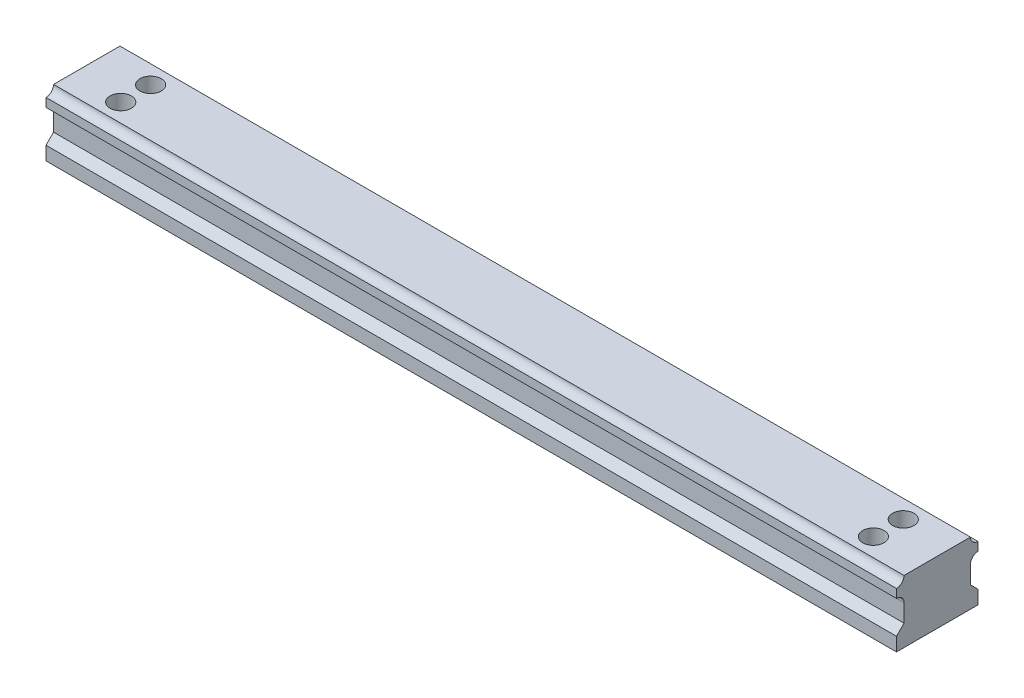
SolidWorks part; units mm, degrees
ref_plane "Front Plane" through (0, 0, 0) normal (0, 0, 1) x (1, 0, 0)
ref_plane "Top Plane" through (0, 0, 0) normal (0, 1, 0) x (1, 0, 0)
ref_plane "Right Plane" through (0, 0, 0) normal (1, 0, 0) x (0, 0, -1)
sketch "Sketch1" plane through (0, 0, 0) normal (1, 0, 0) x (0, 0, -1)
  line L0 (0, 0) -> (30, 0)
  line L1 (0, 0) -> (0, 5)
  line L2 (0, 5) -> (2.7781, 7.7781)
  line L3 (2.7781, 7.7781) -> (2.7781, 14.2781)
  line L4 (2.7781, 14.2781) -> (0, 14.2781) construction
  line L5 (0, 14.2781) -> (0, 23) construction
  line L6 (0, 23) -> (30, 23) construction
  line L12 (15, 0) -> (15, 23) construction
  line L13 (27.2219, 23) -> (2.7781, 23)
  line L14 (0, 20.2219) -> (0, 17.0562)
  line L15 (30, 14.2781) -> (30, 23) construction
  line L16 (27.2219, 14.2781) -> (30, 14.2781) construction
  line L17 (30, 20.2219) -> (30, 17.0562)
  line L18 (27.2219, 7.7781) -> (27.2219, 14.2781)
  line L19 (30, 5) -> (27.2219, 7.7781)
  line L20 (30, 0) -> (30, 5)
  arc A0 (2.7781, 14.2781) -> (0, 17.0562) centre (0, 14.2781) ccw
  arc A1 (0, 20.2219) -> (2.7781, 23) centre (0, 23) ccw
  arc A2 (30, 20.2219) -> (27.2219, 23) centre (30, 23) cw
  arc A3 (27.2219, 14.2781) -> (30, 17.0562) centre (30, 14.2781) cw
  dimension "D1" = 5.5563
  dimension "D2" = 15
  dimension "D3" = 23
  dimension "D4" = 45
  dimension "D5" = 6.5
  dimension "D6" = 5
extrude "Boss-Extrude1" add sketch "Sketch1" along normal blind 312.998
sketch "Sketch2" plane through (0, 23, 0) normal (0, 1, 0) x (1, 0, 0)
  line L0 (0, 30) -> (156.499, 116.4954) construction
  line L1 (156.499, 116.4954) -> (312.998, 30) construction
  line L2 (312.998, 30) -> (156.499, -38.2063) construction
  line L3 (156.499, -38.2063) -> (156.499, 116.4954) construction
  line L4 (312.998, 30) -> (294.998, 20.5) construction
  line L5 (294.998, 20.5) -> (294.998, 9.5) construction
  line L6 (294.998, 9.5) -> (312.998, 0) construction
  line L7 (312.998, 27.2219) -> (312.998, 2.7781) construction
  line L8 (312.998, 0) -> (0, 0) construction
  circle A0 centre (294.998, 20.5) radius 1.9177
  circle A1 centre (294.998, 9.5) radius 1.9177
  circle A2 centre (18, 9.5) radius 1.9177
  circle A3 centre (18, 20.5) radius 1.9177
  dimension "D1" = 3.8354
  dimension "D2" = 18
  dimension "D3" = 9.5
extrude "Cut-Extrude1" cut sketch "Sketch2" against normal through all
sketch "Sketch3" plane through (0, 23, 0) normal (0, 1, 0) x (1, 0, 0)
  circle A0 centre (18, 20.5) radius 3.9306
  circle A1 centre (18, 9.5) radius 3.9306
  circle A2 centre (294.998, 9.5) radius 3.9306
  circle A3 centre (294.998, 20.5) radius 3.9306
  dimension "D1" = 7.8613
extrude "Cut-Extrude2" cut sketch "Sketch3" against normal blind 7.302
